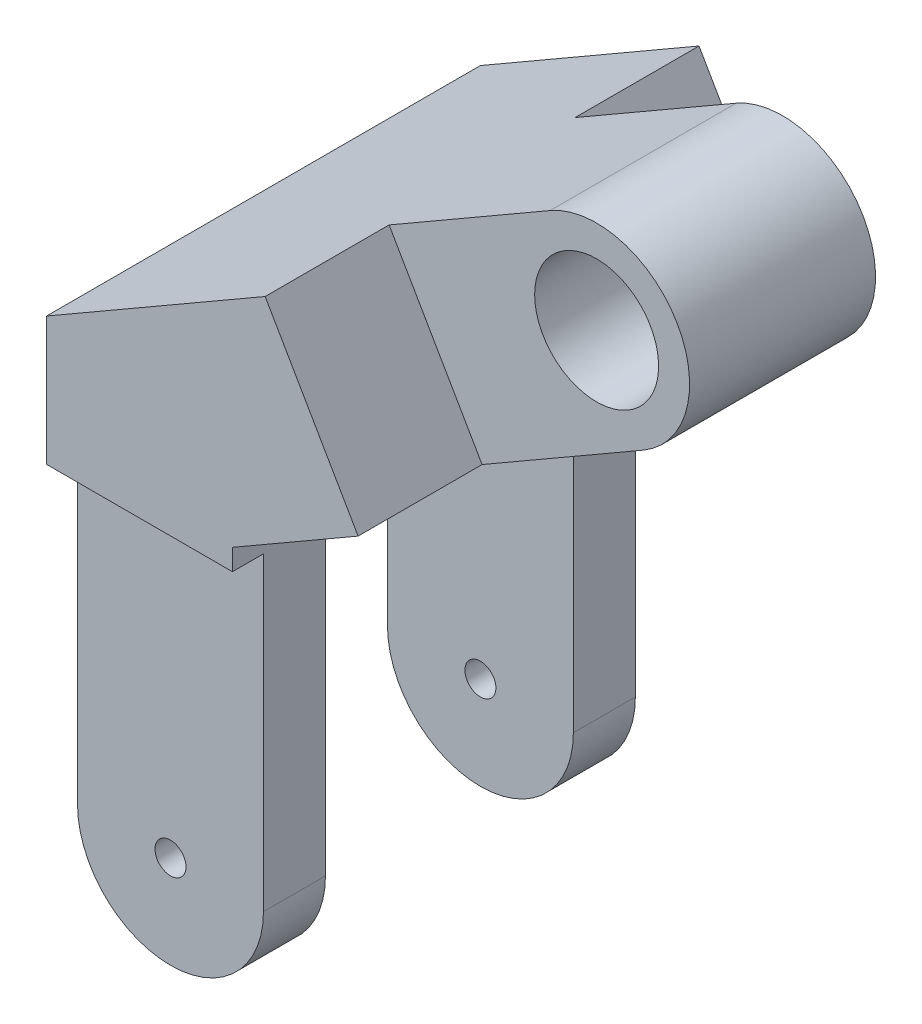
SolidWorks part; units mm, degrees
ref_plane "前视基准面" through (0, 0, 0) normal (0, 0, 1) x (1, 0, 0)
ref_plane "上视基准面" through (0, 0, 0) normal (0, 1, 0) x (1, 0, 0)
ref_plane "右视基准面" through (0, 0, 0) normal (1, 0, 0) x (0, 0, -1)
other "Configuration Table"
sketch "草图1" plane through (0, 0, 0) normal (0, 0, 1) x (1, 0, 0)
  line L0 (0, 0) -> (0, 62.0652) construction
  line L1 (0, 62.0652) -> (53.75, 93.0977) construction
  line L2 (53.75, 93.0977) -> (0, 0) construction
  line L3 (-15, 0) -> (-15, 70.7254)
  line L4 (-15, 70.7254) -> (46.25, 106.0881)
  line L5 (61.25, 80.1073) -> (15, 53.4049)
  line L6 (15, 0) -> (15, 53.4049)
  arc A0 (-15, 0) -> (15, 0) centre (0, 0) ccw
  arc A1 (61.25, 80.1073) -> (46.25, 106.0881) centre (53.75, 93.0977) ccw
  circle A2 centre (0, 0) radius 2.5
  circle A3 centre (53.75, 93.0977) radius 10
  dimension "D1" = 30
  dimension "D2" = 30
  dimension "D6" = 20
  dimension "D7" = 5
  dimension "D3" = 107.5
  dimension "D4" = 30
  dimension "D5" = 30
extrude "凸台-拉伸1" add sketch "草图1" along normal blind 70
sketch "草图2" plane through (-34.375, 59.5392, 0) normal (-0.5, 0.866, 0) x (0.866, 0.5, 0)
  line L0 (-35.5646, -35) -> (128.3076, -35) construction
  line L1 (93.0977, -70) -> (22.3723, -70) construction
  line L2 (93.0977, 0) -> (22.3723, 0) construction
  line L3 (63.0977, 10) -> (63.0977, -20)
  line L4 (123.0977, -80) -> (63.0977, -80)
  line L5 (123.0977, -80) -> (123.0977, -50)
  line L6 (123.0977, -50) -> (63.0977, -50)
  line L7 (63.0977, -80) -> (63.0977, -50)
  line L8 (123.0977, -20) -> (63.0977, -20)
  line L9 (123.0977, 10) -> (123.0977, -20)
  line L10 (123.0977, 10) -> (63.0977, 10)
  line L11 (93.0977, -70) -> (93.0977, 0) construction
  dimension "D1" = 30
  dimension "D2" = 60
  dimension "D3" = 30
  dimension "D4" = 30
extrude "切除-拉伸1" cut sketch "草图2" against normal blind 70
sketch "草图3" plane through (15, 0, 0) normal (1, 0, 0) x (0, 0, -1)
  line L0 (-35, -22.7241) -> (-35, 25.3192) construction
  line L1 (0, 0) -> (0, 53.4049) construction
  line L2 (-70, 0) -> (-70, 53.4049) construction
  line L3 (-55, -20) -> (-55, 50)
  line L4 (15, -20) -> (-5, -20)
  line L5 (15, -20) -> (15, 50)
  line L6 (15, 50) -> (-5, 50)
  line L7 (-5, -20) -> (-5, 50)
  line L8 (-55, -20) -> (-15, -20)
  line L9 (-35, -20) -> (-35, 50)
  line L10 (-55, 50) -> (-15, 50)
  line L11 (-15, -20) -> (-15, 50)
  line L12 (-65, -20) -> (-65, 50)
  line L13 (-85, 50) -> (-65, 50)
  line L14 (-85, -20) -> (-85, 50)
  line L15 (-85, -20) -> (-65, -20)
  line L16 (-70, 0) -> (0, 0) construction
  dimension "D1" = 5
  dimension "D2" = 20
  dimension "D3" = 50
  dimension "D4" = 20
  dimension "D5" = 40
extrude "切除-拉伸2" cut sketch "草图3" against normal blind 70 contours L5 L6 L7 L4 | L8 L11 L10 L3 | L15 L12 L13 L14
